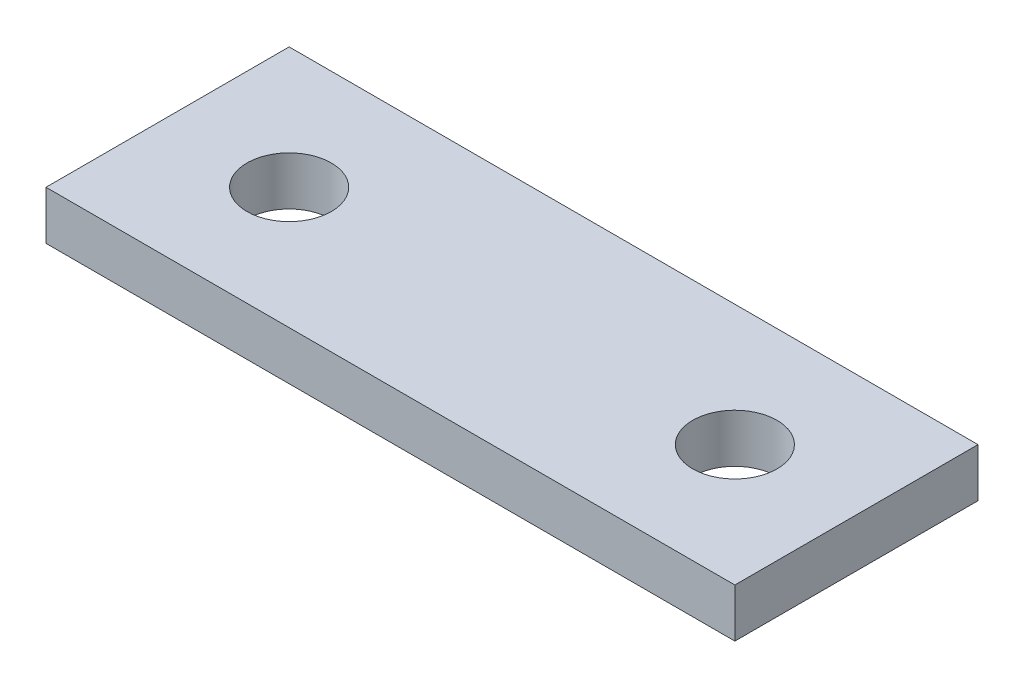
SolidWorks part; units mm, degrees
ref_plane "Спереди" through (0, 0, 0) normal (0, 0, 1) x (1, 0, 0)
ref_plane "Сверху" through (0, 0, 0) normal (0, 1, 0) x (1, 0, 0)
ref_plane "Справа" through (0, 0, 0) normal (1, 0, 0) x (0, 0, -1)
sketch "Эскиз1" plane through (0, 0, 0) normal (0, 1, 0) x (1, 0, 0)
  line L1 (-21.25, 7.5) -> (21.25, 7.5)
  line L2 (-21.25, 7.5) -> (-21.25, -7.5)
  line L3 (-21.25, -7.5) -> (21.25, -7.5)
  line L4 (21.25, 7.5) -> (21.25, -7.5)
  line L5 (-21.25, 7.5) -> (21.25, -7.5) construction
  line L6 (-21.25, -7.5) -> (21.25, 7.5) construction
  circle A1 centre (13.75, 0) radius 2.6
  circle A2 centre (-13.75, 0) radius 2.6
  point P0 (0, 0)
  point P12 (0, 0)
extrude "Бобышка-Вытянуть1" add sketch "Эскиз1" along normal blind 3
